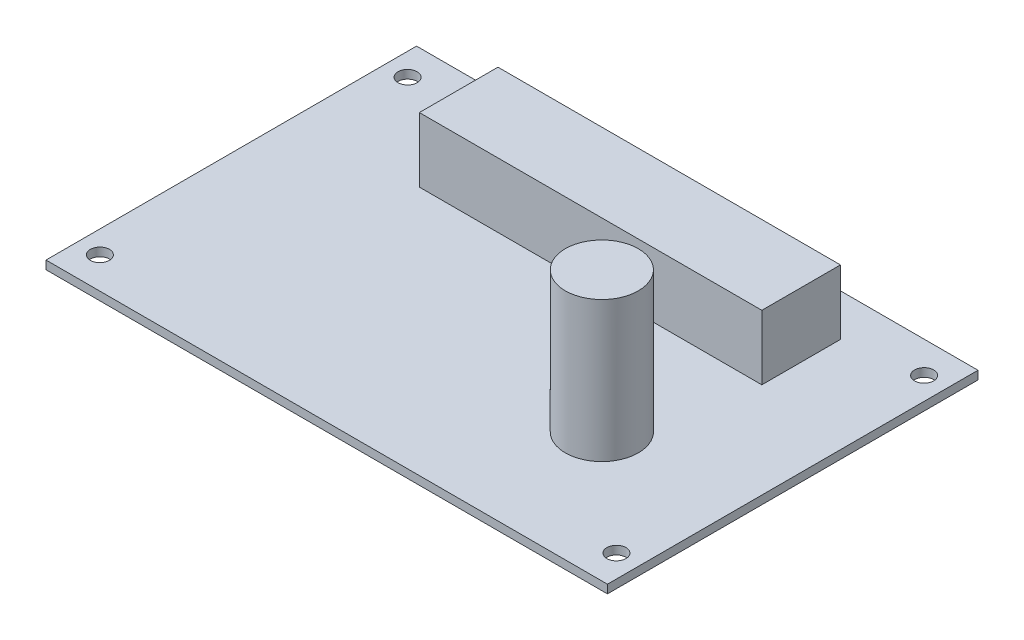
SolidWorks part; units mm, degrees
ref_plane "Ebene vorne" through (0, 0, 0) normal (0, 0, 1) x (1, 0, 0)
ref_plane "Ebene oben" through (0, 0, 0) normal (0, 1, 0) x (1, 0, 0)
ref_plane "Ebene rechts" through (0, 0, 0) normal (1, 0, 0) x (0, 0, -1)
sketch "Skizze1" plane through (0, 0, 0) normal (0, 1, 0) x (1, 0, 0)
  line L1 (-50, -33) -> (50, -33)
  line L2 (-50, -33) -> (-50, 33)
  line L3 (-50, 33) -> (50, 33)
  line L4 (50, -33) -> (50, 33)
  line L5 (-50, -33) -> (50, 33) construction
  line L6 (-50, 33) -> (50, -33) construction
  point P0 (0, 0)
  dimension "D1" = 100
  dimension "D2" = 66
extrude "Aufsatz-Linear austragen1" add sketch "Skizze1" along normal blind 1.5
sketch "Skizze2" plane through (0, 1.5, 0) normal (0, 1, 0) x (1, 0, 0)
  line L0 (50, 33) -> (-50, 33) construction
  line L1 (-28, 25.5) -> (33, 25.5)
  line L2 (-28, 25.5) -> (-28, 11.5)
  line L3 (-28, 11.5) -> (33, 11.5)
  line L4 (33, 25.5) -> (33, 11.5)
  line L5 (50, -33) -> (50, 33) construction
  dimension "D1" = 61
  dimension "D2" = 14
  dimension "D3" = 7.5
  dimension "D4" = 17
extrude "Aufsatz-Linear austragen2" add sketch "Skizze2" along normal blind 11.5
sketch "Skizze3" plane through (0, 1.5, 0) normal (0, 1, 0) x (1, 0, 0)
  line L0 (50, -33) -> (50, 33) construction
  line L1 (-50, -33) -> (50, -33) construction
  circle A0 centre (26, -10) radius 6.5
  dimension "D1" = 13
  dimension "D2" = 24
  dimension "D3" = 23
extrude "Aufsatz-Linear austragen3" add sketch "Skizze3" along normal blind 25
hole_wizard "Durchgangsloch für M31" positions "Skizze4" profile "Skizze5" hole size "M3" standard "DIN" end condition through all
sketch "Skizze4" plane through (0, 1.5, 0) normal (0, 1, 0) x (1, 0, 0)
  line L0 (-46, -27.4008) -> (-46, 27.4008) construction
  line L1 (-46, 27.4008) -> (46, 27.4008) construction
  line L2 (46, 27.4008) -> (46, -27.4008) construction
  line L3 (46, -27.4008) -> (-46, -27.4008) construction
  line L4 (-46, -27.4008) -> (-50, -27.4008) construction
  line L5 (-50, 33) -> (-50, -33) construction
  line L8 (46, -27.4008) -> (50, -27.4008) construction
  line L9 (50, -33) -> (50, 33) construction
  line L11 (46, -27.4008) -> (46, -33) construction
  line L12 (-50, -33) -> (50, -33) construction
  line L15 (46, 27.4008) -> (46, 33) construction
  line L16 (50, 33) -> (-50, 33) construction
  point P0 (-46, -27.4008)
  point P2 (-46, 27.4008)
  point P4 (46, 27.4008)
  point P6 (46, -27.4008)
  point P39 (0, 0)
  point P40 (-46, -14.678)
  point P41 (0, 0)
  dimension "D1" = 54.8016
  dimension "D2" = 92
sketch "Skizze5" plane through (-46, 1.5, 27.4008) normal (1, 0, 0) x (0, 0, 1)
  line L0 (0, 0) -> (0, 1.5)
  line L1 (0, 1.5) -> (1.7, 1.5)
  line L2 (1.7, 1.5) -> (1.7, 0)
  line L5 (1.7, 0) -> (0, 0)
  line L11 (0, -6.35) -> (0, 107.95) construction
  dimension "Bohrerdurchmesser" = 3.4
  dimension "Bohrungstiefe" = 1.5
